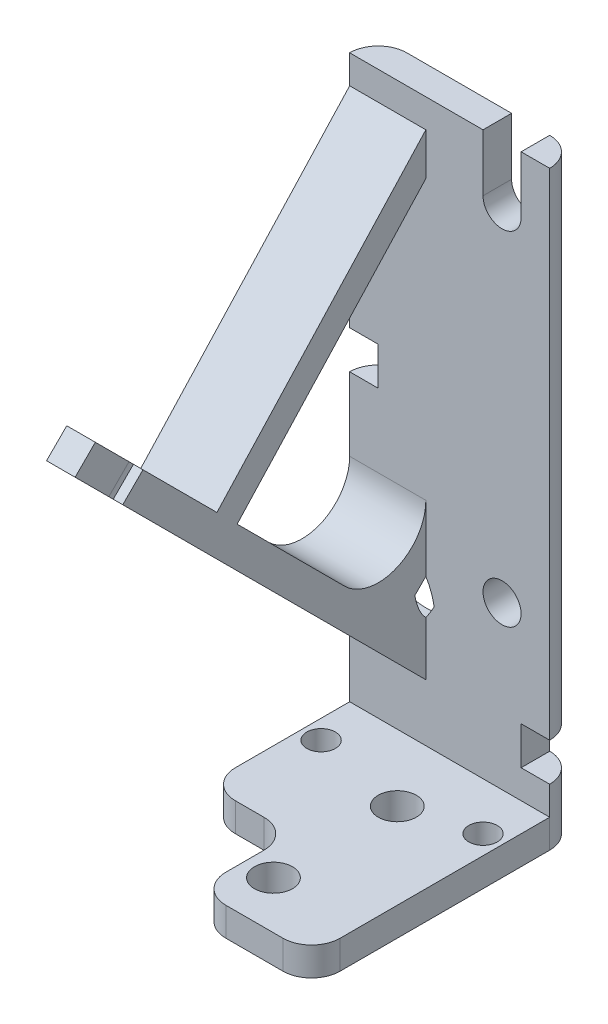
SolidWorks part; units mm, degrees
ref_plane "前视基准面" through (0, 0, 0) normal (0, 0, 1) x (1, 0, 0)
ref_plane "上视基准面" through (0, 0, 0) normal (0, 1, 0) x (1, 0, 0)
ref_plane "右视基准面" through (0, 0, 0) normal (1, 0, 0) x (0, 0, -1)
sketch "草图1" plane through (0, 0, 0) normal (0, 1, 0) x (1, 0, 0)
  line L0 (0, 0) -> (-31.0731, 0) construction
  line L1 (0, 0) -> (0, -20) construction
  line L2 (-12, 0) -> (-12, 8)
  line L3 (-12, 8) -> (9, 8)
  line L4 (9, 8) -> (9, -20)
  line L5 (9, -20) -> (0, -20)
  line L7 (-12, 0) -> (-12, -20)
  line L8 (-12, -20) -> (0, -20)
  line L9 (0, -2) -> (-10, -2) construction
  line L10 (-10, -2) -> (-10, 0) construction
  line L11 (-5, -2) -> (-5, 2.0521) construction
  line L12 (-1.5, 8) -> (-1.5, -24.322) construction
  circle A0 centre (0, -15) radius 2
  circle A4 centre (-10, 0) radius 1.5
  circle A5 centre (0, -2) radius 2
  circle A6 centre (7, 0) radius 1.5
  dimension "D1" = 4
  dimension "D9" = 4
  dimension "D10" = 3
  dimension "D2" = 13
  dimension "D3" = 5
  dimension "D4" = 8
  dimension "D5" = 14
  dimension "D6" = 7
  dimension "D7" = 20
  dimension "D8" = 10
extrude "凸台-拉伸1" add sketch "草图1" along normal blind 3
sketch "草图3" plane through (0, 3, 0) normal (0, 1, 0) x (1, 0, 0)
  line L0 (-10, 0) -> (0, 0) construction
  line L1 (0, 0) -> (0, -2) construction
  line L2 (12.1019, -5.5) -> (-16.4953, -5.5) construction
  line L3 (9, -20) -> (9, 8) construction
  line L4 (-9, 5) -> (9, 5)
  line L5 (-9, 5) -> (-9, 8)
  line L6 (-9, 8) -> (9, 8)
  line L7 (9, 5) -> (9, 8)
  line L8 (-9, 5) -> (9, 8) construction
  line L9 (-9, 8) -> (9, 5) construction
  line L10 (9, 8) -> (-12, 8) construction
  point P8 (0, 6.5)
  dimension "D1" = 3
extrude "凸台-拉伸3" add sketch "草图3" along normal blind 56
sketch "草图4" plane through (0, 0, -5) normal (0, 0, 1) x (1, 0, 0)
  line L0 (4, 20) -> (4, 56) construction
  line L1 (-9, 59) -> (9, 59) construction
  line L2 (9, 59) -> (9, 3) construction
  circle A0 centre (4, 56) radius 2
  circle A1 centre (4, 20) radius 2
  dimension "D1" = 4
  dimension "D4" = 4
  dimension "D2" = 36
  dimension "D3" = 3
  dimension "D5" = 5
extrude "切除-拉伸1" cut sketch "草图4" against normal through all
fillet "圆角1" radius 3 4 edges at (-12, 1.5, -8) (-12, 1.5, 20) (9, 1.5, 20) (9, 29.5, -8)
sketch "草图5" plane through (-12, 0, 0) normal (-1, 0, 0) x (0, 0, 1)
  line L2 (-5, 13.2426) -> (22.5772, 40.8198)
  line L8 (22.5772, 40.8198) -> (24.6985, 38.6985)
  line L10 (24.6985, 38.6985) -> (-5, 9)
  line L11 (-8, 59) -> (-8, 3)
  line L15 (-5, 59) -> (-5, 3) construction
  line L19 (-5, 13.2426) -> (-5, 59)
  line L20 (-5, 59) -> (-8, 59)
  line L21 (-5, 4.8734) -> (44.6449, 4.8734) construction
  line L24 (-5, 3) -> (17, 3) construction
  line L25 (-5, 9) -> (-5, 3)
  line L26 (-5, 3) -> (-8, 3)
  dimension "D1" = 45
  dimension "D2" = 3
  dimension "D3" = 6
  dimension "D4" = 42
extrude "凸台-拉伸4" add sketch "草图5" against normal blind 8
sketch "草图8" plane through (0, 7, -7) normal (0, -0.7071, 0.7071) x (1, 0, 0)
  line L0 (-4, 44.8284) -> (-12, 44.8284) construction
  line L1 (-7, 41.4305) -> (-7, 43.4305) construction
  line L2 (-5, 42.8284) -> (-5, 44.8284)
  line L3 (-4, 44.8284) -> (-12, 44.8284) construction
  line L4 (-5, 44.8284) -> (-9, 44.8284)
  line L5 (-9, 44.8284) -> (-9, 42.8284)
  line L6 (-4, 2.8284) -> (-4, 44.8284) construction
  arc A0 (-9, 42.8284) -> (-5, 42.8284) centre (-7, 42.8284) ccw
  circle A1 centre (-7, 6.8284) radius 2
  dimension "D1" = 4
  dimension "D4" = 4
  dimension "D2" = 2
  dimension "D3" = 36
  dimension "D5" = 3
extrude "切除-拉伸4" cut sketch "草图8" against normal offset from surface (2 mm away) 1 up to face at (-8, 27.0312, 8.7886)
fillet "圆角2" radius 3 1 edges at (-12, 31, -8)
fillet "圆角3" radius 5 1 edges at (-8, 13.2426, -5)
sketch "草图9" plane through (-12, 0, 0) normal (-1, 0, 0) x (0, 0, 1)
  line L1 (22.5772, 40.8198) -> (3.5355, 21.7782) construction
  line L2 (14.8101, 33.0528) -> (17.2336, 34.8497)
  line L6 (24.6985, 38.6985) -> (22.5772, 40.8198) construction
  line L7 (17.2336, 34.8497) -> (-5, 59)
  line L8 (-5, 59) -> (-5, 54.5707)
  line L9 (-5, 25.3137) -> (-5, 59) construction
  line L10 (-5, 54.5707) -> (14.8101, 33.0528)
  dimension "D1" = 3
  dimension "D2" = 8
extrude "凸台-拉伸5" add sketch "草图9" against normal up to surface (8 mm away) up to face at (-4, 26.5517, 7.926)
sketch "草图10" plane through (0, 7, -7) normal (0, -0.7071, 0.7071) x (1, 0, 0)
  line L0 (-5, 42.8284) -> (-5, 44.8284)
  line L1 (-5, 44.8284) -> (-9, 44.8284)
  line L2 (-9, 44.8284) -> (-9, 42.8284)
  circle A0 centre (-7, 6.8284) radius 2 construction
  circle A1 centre (-7, 42.8284) radius 2 construction
  circle A2 centre (-7, 6.8284) radius 2
  arc A3 (-9, 42.8284) -> (-5, 42.8284) centre (-7, 42.8284) ccw
extrude "切除-拉伸5" cut sketch "草图10" against normal through all
ref_plane "基准面1" through (0, 21.1421, -21.1421) normal (0, -0.7071, 0.7071) x (-1, 0, 0)
sketch "草图11" plane through (0, 21.1421, -21.1421) normal (0, -0.7071, 0.7071) x (-1, 0, 0)
  circle A0 centre (7, -6.8284) radius 4
  dimension "D1" = 8
extrude "切除-拉伸6" cut sketch "草图11" along normal offset from surface (15 mm away) 5 up to face at (-7, 10.4142, -3.5858)
sketch "草图13" plane through (0, 0, 0) normal (0, -1, 0) x (1, 0, 0)
  line L0 (-7.938, 24.5333) -> (-7.938, 3.4077) construction
  line L1 (-12, -5) -> (-12, 17) construction
  line L2 (-12, 10) -> (-3, 10)
  line L3 (-12, 10) -> (-12, 20)
  line L4 (-12, 20) -> (-3, 20)
  line L5 (-3, 10) -> (-3, 20)
  line L6 (-9, 20) -> (6, 20) construction
  ellipse E0 centre (-7, 23.2843) end of major axis (-5, 23.2843) minor radius 1.4142 (-9, 23.2843) -> (-5, 23.2843) ccw construction
  dimension "D1" = 10
  dimension "D2" = 9
extrude "切除-拉伸7" cut sketch "草图13" against normal up to next
fillet "圆角4" radius 3 3 edges at (-3, 1.5, 20) (-12, 1.5, 10) (-3, 1.5, 10)
sketch "草图14" plane through (0, 0, -5) normal (0, 0, 1) x (1, 0, 0)
  line L0 (2, 56) -> (2, 60.6487)
  line L2 (6, 56) -> (6, 60.6487)
  line L3 (6, 60.6487) -> (2, 60.6487)
  line L4 (2, 56) -> (6, 56)
  line L5 (2, 56) -> (2, 60.6487) construction
  circle A0 centre (4, 56) radius 2 construction
extrude "切除-拉伸8" cut sketch "草图14" against normal through all
chamfer "倒角1" distance 2 angle 45 1 edges at (-7, 13.9497, -7.1213)
sketch "草图15" plane through (0, 31.6985, 31.6985) normal (0, 0.7071, 0.7071) x (1, 0, 0)
  line L0 (-4, 12.8995) -> (-5, 12.8995) construction
  line L1 (-5, 12.8995) -> (-5, 9.8995) construction
  line L2 (-5, 9.8995) -> (-4, 9.8995) construction
  line L3 (-4, 9.8995) -> (-4, 12.8995) construction
  line L4 (-9, 9.8995) -> (-9, 12.8995) construction
  line L5 (-9, 12.8995) -> (-12, 12.8995) construction
  line L6 (-12, 12.8995) -> (-12, 9.8995) construction
  line L7 (-12, 9.8995) -> (-9, 9.8995) construction
  line L8 (-4, 12.8995) -> (-5, 12.8995)
  line L9 (-5, 12.8995) -> (-5, 9.8995)
  line L10 (-5, 9.8995) -> (-4, 9.8995)
  line L11 (-4, 9.8995) -> (-4, 12.8995)
  line L12 (-9, 9.8995) -> (-9, 12.8995)
  line L13 (-9, 12.8995) -> (-12, 12.8995)
  line L14 (-12, 12.8995) -> (-12, 9.8995)
  line L15 (-12, 9.8995) -> (-9, 9.8995)
extrude "凸台-拉伸6" add sketch "草图15" along normal blind 3
sketch "草图16" plane through (0, 59, 0) normal (0, 1, 0) x (1, 0, 0)
  line L2 (6, 8) -> (6, 5)
  line L3 (6, 5) -> (9, 5)
  line L4 (-4, 5) -> (2, 5)
  line L5 (2, 5) -> (2, 8)
  line L6 (2, 8) -> (-9, 8)
  line L7 (-12, 5) -> (-4, 5)
  line L8 (-4, 5) -> (2, 5)
  line L9 (2, 5) -> (2, 8)
  line L10 (2, 8) -> (-9, 8)
  line L11 (-12, 5) -> (-4, 5)
  line L12 (6, 8) -> (6, 5)
  line L13 (6, 5) -> (9, 5)
  arc A1 (-9, 8) -> (-12, 5) centre (-9, 5) ccw
  arc A3 (9, 5) -> (6, 8) centre (6, 5) ccw
  arc A4 (9, 5) -> (6, 8) centre (6, 5) ccw
  arc A5 (-9, 8) -> (-12, 5) centre (-9, 5) ccw
  dimension "D1" = 0
  dimension "D2" = 0
extrude "凸台-拉伸7" add sketch "草图16" along normal blind 3
sketch "草图18" plane through (0, 0, -8) normal (0, 0, -1) x (-1, 0, 0)
  line L0 (12, 25.3137) -> (12, 54.5707) construction
  line L1 (12, 37) -> (9, 37)
  line L2 (12, 37) -> (12, 33)
  line L3 (12, 33) -> (9, 33)
  line L4 (9, 37) -> (9, 33)
  line L5 (12, 62) -> (9, 62) construction
  line L6 (-9, 62) -> (-9, 3) construction
  line L7 (-9, 6) -> (-6, 6)
  line L8 (-9, 6) -> (-9, 10)
  line L9 (-9, 10) -> (-6, 10)
  line L10 (-6, 6) -> (-6, 10)
  line L11 (-9, 0) -> (-6, 0) construction
  dimension "D1" = 4
  dimension "D2" = 3
  dimension "D3" = 25
  dimension "D4" = 4
  dimension "D5" = 3
  dimension "D6" = 6
extrude "切除-拉伸9" cut sketch "草图18" against normal blind 3
